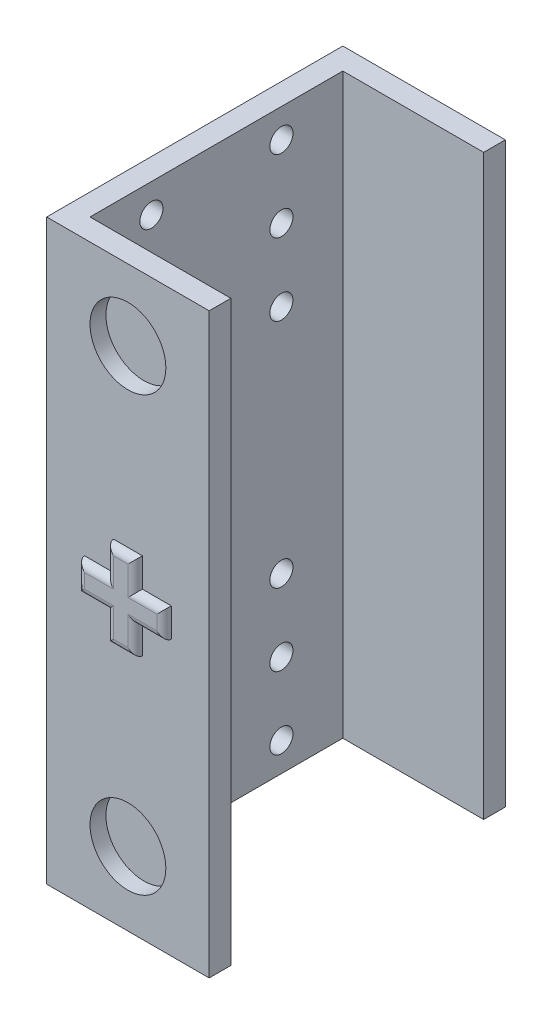
SolidWorks part; units mm, degrees
ref_plane "Plan de face" through (0, 0, 0) normal (0, 0, 1) x (1, 0, 0)
ref_plane "Plan de dessus" through (0, 0, 0) normal (0, 1, 0) x (1, 0, 0)
ref_plane "Plan de droite" through (0, 0, 0) normal (1, 0, 0) x (0, 0, -1)
sketch "Esquisse1" plane through (0, 0, 0) normal (0, 0, 1) x (1, 0, 0)
  line L1 (0, 0) -> (22.5, 0)
  line L2 (0, 0) -> (0, 80)
  line L3 (0, 80) -> (22.5, 80)
  line L4 (22.5, 0) -> (22.5, 80)
  dimension "D1" = 22.5
  dimension "D2" = 80
extrude "Boss.-Extru.1" add sketch "Esquisse1" along normal blind 3
sketch "Esquisse2" plane through (0, 0, 3) normal (0, 0, 1) x (1, 0, 0)
  line L0 (22.5, 80) -> (0, 80) construction
  line L1 (0, 0) -> (3, 0)
  line L2 (0, 0) -> (0, 80)
  line L3 (0, 80) -> (3, 80)
  line L4 (3, 0) -> (3, 80)
  dimension "D1" = 3
extrude "Boss.-Extru.2" add sketch "Esquisse2" along normal blind 35
sketch "Esquisse3" plane through (0, 0, 38) normal (0, 0, 1) x (1, 0, 0)
  line L2 (0, 0) -> (22.5, 0)
  line L3 (0, 0) -> (0, 80)
  line L4 (0, 80) -> (22.5, 80)
  line L5 (22.5, 0) -> (22.5, 80)
extrude "Boss.-Extru.3" add sketch "Esquisse3" along normal blind 3
sketch "Esquisse4" plane through (0, 0, 0) normal (0, 0, -1) x (-1, 0, 0)
  line L0 (0, 0) -> (-22.5, 0) construction
  line L1 (0, 80) -> (0, 0) construction
  circle A0 centre (-11.25, 10.15) radius 5.25
  circle A1 centre (-11.25, 70.15) radius 5.25
  point P8 (-17.1094, 23.397)
  dimension "D1" = 10.5
  dimension "D2" = 10.5
  dimension "D3" = 10.15
  dimension "D4" = 60
  dimension "D5" = 11.25
  dimension "D6" = 11.25
extrude "Enlèv. mat.-Extru.1" cut sketch "Esquisse4" against normal blind 2.2
sketch "Esquisse5" plane through (0, 0, 3) normal (0, 0, 1) x (1, 0, 0)
  line L0 (-25.6121, 40) -> (52.8895, 40) construction
  line L2 (22.5, 80) -> (0, 80) construction
  line L3 (0, 0) -> (22.5, 0) construction
  line L4 (11.25, -6.6596) -> (11.25, 93.0528) construction
  line L5 (22.5, 0) -> (22.5, 80) construction
  line L6 (4.5, 37.75) -> (9, 37.75)
  line L7 (9, 37.75) -> (9, 33.25)
  line L8 (9, 33.25) -> (13.5, 33.25)
  line L9 (13.5, 33.25) -> (13.5, 37.75)
  line L10 (13.5, 37.75) -> (18, 37.75)
  line L11 (18, 37.75) -> (18, 42.25)
  line L12 (18, 42.25) -> (13.5, 42.25)
  line L15 (13.5, 42.25) -> (13.5, 46.75)
  line L16 (13.5, 46.75) -> (9, 46.75)
  line L17 (9, 46.75) -> (9, 42.25)
  line L18 (9, 42.25) -> (4.5, 42.25)
  line L19 (4.5, 42.25) -> (4.5, 37.75)
  dimension "D1" = 40
  dimension "D2" = 40
  dimension "D3" = 11.25
  dimension "D4" = 2.25
  dimension "D5" = 2.25
  dimension "D6" = 4.5
  dimension "D7" = 4.5
  dimension "D8" = 4.5
  dimension "D9" = 4.5
  dimension "D10" = 4.5
  dimension "D11" = 4.5
  dimension "D12" = 4.5
  dimension "D13" = 4.5
  dimension "D14" = 4.5
  dimension "D15" = 4.5
  dimension "D16" = 4.5
extrude "Enlèv. mat.-Extru.2" cut sketch "Esquisse5" against normal blind 1.2 from offset 1.8 offset against normal yes
sketch "Esquisse6" plane through (0, 0, 41) normal (0, 0, 1) x (1, 0, 0)
  line L0 (22.5, 0) -> (22.5, 80) construction
  line L1 (0, 0) -> (22.5, 0) construction
  circle A0 centre (11.25, 10.15) radius 5.25
  circle A1 centre (11.25, 70.15) radius 5.25
  dimension "D1" = 10.5
  dimension "D4" = 10.5
  dimension "D2" = 11.25
  dimension "D3" = 10.15
  dimension "D5" = 60
  dimension "D6" = 11.25
extrude "Enlèv. mat.-Extru.3" cut sketch "Esquisse6" against normal blind 2.2
sketch "Esquisse7" plane through (0, 0, 41) normal (0, 0, 1) x (1, 0, 0)
  line L0 (11.25, 87.4794) -> (11.25, -8.0428) construction
  line L1 (22.5, 0) -> (22.5, 80) construction
  line L2 (-34.624, 40) -> (69.7536, 40) construction
  line L3 (22.5, 80) -> (0, 80) construction
  line L5 (0, 0) -> (22.5, 0) construction
  line L6 (5.25, 42) -> (9.25, 42)
  line L7 (9.25, 42) -> (9.25, 46)
  line L8 (9.25, 46) -> (13.25, 46)
  line L9 (13.25, 46) -> (13.25, 42)
  line L11 (13.25, 42) -> (17.25, 42)
  line L12 (17.25, 42) -> (17.25, 38)
  line L14 (17.25, 38) -> (13.25, 38)
  line L15 (13.25, 38) -> (13.25, 34)
  line L16 (13.25, 34) -> (9.25, 34)
  line L17 (9.25, 34) -> (9.25, 38)
  line L18 (9.25, 38) -> (5.25, 38)
  line L19 (5.25, 38) -> (5.25, 42)
  dimension "D1" = 11.25
  dimension "D2" = 40
  dimension "D3" = 40
  dimension "D4" = 4
  dimension "D5" = 4
  dimension "D6" = 4
  dimension "D7" = 4
  dimension "D8" = 2
  dimension "D9" = 2
  dimension "D10" = 4
  dimension "D11" = 4
  dimension "D12" = 4
  dimension "D13" = 4
  dimension "D14" = 4
  dimension "D15" = 4
extrude "Boss.-Extru.4" add sketch "Esquisse7" along normal blind 1
sketch "Esquisse8" plane through (0, 0, 0) normal (-1, 0, 0) x (0, 0, 1)
  line L0 (0, 80) -> (0, 0) construction
  line L1 (41, 80) -> (0, 80) construction
  line L2 (41, 0) -> (0, 0) construction
  circle A0 centre (29.5, 76) radius 1.6
  circle A1 centre (29.5, 66) radius 1.6
  circle A2 centre (29.5, 56) radius 1.6
  circle A3 centre (11.5, 76) radius 1.6
  circle A4 centre (11.5, 66) radius 1.6
  circle A5 centre (11.5, 56) radius 1.6
  circle A6 centre (11.5, 4) radius 1.6
  circle A7 centre (11.5, 14) radius 1.6
  circle A8 centre (11.5, 24) radius 1.6
  circle A9 centre (29.5, 24) radius 1.6
  circle A10 centre (29.5, 14) radius 1.6
  circle A11 centre (29.5, 4) radius 1.6
  dimension "D2" = 3.2
  dimension "D6" = 3.2
  dimension "D9" = 3.2
  dimension "D10" = 3.2
  dimension "D11" = 3.2
  dimension "D12" = 3.2
  dimension "D19" = 3.2
  dimension "D20" = 3.2
  dimension "D21" = 3.2
  dimension "D22" = 3.2
  dimension "D23" = 3.2
  dimension "D24" = 3.2
  dimension "D1" = 29.5
  dimension "D3" = 4
  dimension "D4" = 29.5
  dimension "D5" = 10
  dimension "D7" = 29.5
  dimension "D8" = 10
  dimension "D13" = 10
  dimension "D14" = 10
  dimension "D15" = 4
  dimension "D16" = 11.5
  dimension "D17" = 11.5
  dimension "D18" = 11.5
  dimension "D25" = 11.5
  dimension "D26" = 11.5
  dimension "D27" = 11.5
  dimension "D28" = 29.5
  dimension "D29" = 29.5
  dimension "D30" = 29.5
  dimension "D31" = 4
  dimension "D32" = 10
  dimension "D33" = 10
  dimension "10" = 10
  dimension "D34" = 10
  dimension "D35" = 4
extrude "Enlèv. mat.-Extru.4" cut sketch "Esquisse8" against normal blind 4
fillet "Congé2" radius 1 12 edges at (11.25, 46, 42) (9.25, 44, 42) (13.25, 44, 42) (15.25, 42, 42) (17.25, 40, 42) (15.25, 38, 42) (13.25, 36, 42) (9.25, 36, 42) (7.25, 38, 42) (7.25, 42, 42) (5.25, 40, 42) (11.25, 34, 42)
